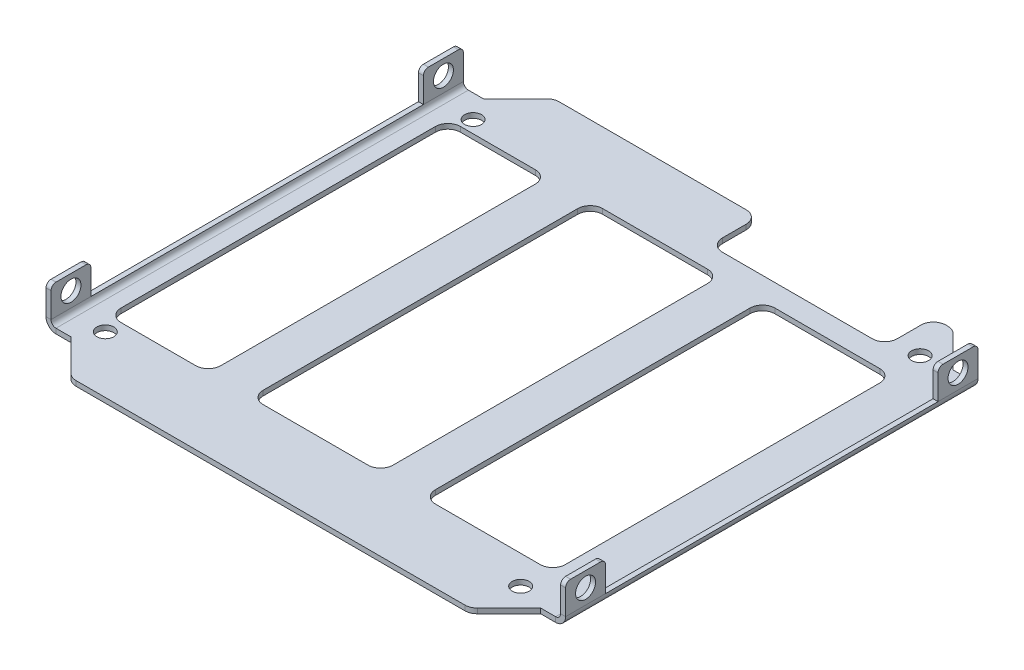
SolidWorks part; units mm, degrees
note: The reader was unsure of these and kept them because the rebuilt part matched: flange length of "Edge-Flange1".
material "6061-T6 (SS)"
ref_plane "Front Plane" through (0, 0, 0) normal (0, 0, 1) x (1, 0, 0)
ref_plane "Top Plane" through (0, 0, 0) normal (0, 1, 0) x (1, 0, 0)
ref_plane "Right Plane" through (0, 0, 0) normal (1, 0, 0) x (0, 0, -1)
sketch "Sketch1" plane through (0, 0, 0) normal (0, 1, 0) x (1, 0, 0)
  line L2 (0, 0) -> (0, 82.6)
  line L4 (104.072, 0) -> (104.072, 82.6)
  line L33 (104.072, 82.6) -> (99.072, 82.6)
  line L37 (5, 82.6) -> (0, 82.6)
  line L38 (5, 82.6) -> (12.0711, 89.6711)
  line L40 (92.0009, 89.6711) -> (99.072, 82.6)
  line L41 (0, 41.3) -> (104.072, 41.3) construction
  line L42 (92.0009, -7.0711) -> (99.072, 0)
  line L43 (12.0711, -7.0711) -> (92.0009, -7.0711)
  line L44 (5, 0) -> (12.0711, -7.0711)
  line L45 (5, 0) -> (0, 0)
  line L46 (104.072, 0) -> (99.072, 0)
  line L47 (88.072, 89.6711) -> (88.072, 79.9211)
  line L48 (88.072, 79.9211) -> (53.072, 79.9211)
  line L49 (53.072, 79.9211) -> (53.072, 89.6711)
  line L50 (53.072, 89.6711) -> (12.0711, 89.6711)
  line L51 (88.072, 89.6711) -> (92.0009, 89.6711)
  line L52 (5, 75.5) -> (5, 7.5)
  line L53 (5, 7.5) -> (94, 7.5)
  line L58 (94, 7.5) -> (94, 75.5)
  line L59 (94, 75.5) -> (5, 75.5)
  dimension "D1" = 82.6
  dimension "D2" = 104.072
  dimension "D3" = 5
  dimension "D4" = 16
  dimension "D5" = 135
  dimension "D6" = 135
  dimension "D7" = 10
  dimension "D8" = 35
  dimension "D9" = 9.75
  dimension "D10" = 41.0009
  dimension "D11" = 68
  dimension "D12" = 89
  dimension "D13" = 7.5
base flange "Base-Flange2" sketch "Sketch1" thickness 1 reverse thickness direction no parameters "D1"=1
edge flange "Edge-Flange1" sketch "Sketch14" flange profiles "Sketch14", "Sketch15" flange angle 90 flange length 8 flange position material inside bend radius 1 thickness 1 relief rectangular parameters "D6"=10, "D8"=1
sketch "Sketch14" plane through (104.072, 0, 0) normal (1, 0, 0) x (0, 0, -1)
  line L0 (0, 0) -> (82.6, 0) construction
  line L1 (0, 0) -> (82.6, 0)
  line L2 (0, 0) -> (0, 7)
  line L3 (0, 7) -> (82.6, 7)
  line L4 (82.6, 7) -> (82.6, 0)
  dimension "D1" = 7
sketch "Sketch15" plane through (0, 0, 0) normal (-1, 0, 0) x (0, 0, 1)
  line L0 (-82.6, 0) -> (0, 0) construction
  line L1 (-82.6, 0) -> (0, 0)
  line L2 (-82.6, 0) -> (-82.6, 7)
  line L3 (-82.6, 7) -> (0, 7)
  line L4 (0, 7) -> (0, 0)
  dimension "D1" = 7
bend "EdgeBend1" bend radius 1 bend angle 90 parameters "D5"=1
bend "EdgeBend2" bend radius 1 bend angle 90 parameters "D5"=2
sketch "Sketch16" plane through (104.072, 0, 0) normal (1, 0, 0) x (0, 0, -1)
  line L0 (82.6, 1) -> (0, 1) construction
  line L1 (8, 8) -> (74.6, 8)
  line L2 (8, 8) -> (8, 1)
  line L3 (8, 1) -> (74.6, 1)
  line L4 (74.6, 8) -> (74.6, 1)
  line L5 (0, 7) -> (0, 1) construction
  line L6 (82.6, 1) -> (82.6, 7) construction
  line L7 (82.6, 7) -> (0, 7) construction
  dimension "D1" = 8
  dimension "D2" = 8
  dimension "D3" = 1
extrude "Cut-Extrude1" cut sketch "Sketch16" against normal through all normal cut yes
fillet "Fillet1" radius 1 8 edges at (0.5, 7, -8) (0.5, 7, 0) (0.5, 7, -74.6) (0.5, 7, -82.6) (103.572, 7, -74.6) (103.572, 7, -82.6) (103.572, 7, 0) (103.572, 7, -8)
sketch "Sketch17" plane through (104.072, 0, 0) normal (1, 0, 0) x (0, 0, -1)
  line L0 (-7.0711, 0) -> (0, 0) construction
  line L1 (0, 6) -> (0, 1) construction
  line L2 (82.6, 0) -> (89.6711, 0) construction
  line L3 (82.6, 1) -> (82.6, 6) construction
  circle A0 centre (4, 4) radius 2
  circle A1 centre (78.6, 4) radius 2
  dimension "D1" = 4
  dimension "D4" = 4
  dimension "D2" = 4
  dimension "D3" = 4
  dimension "D5" = 4
  dimension "D6" = 4
extrude "Cut-Extrude2" cut sketch "Sketch17" against normal through all normal cut yes
hole_wizard "M3 Clearance Hole1" positions "Sketch18" profile "Sketch19" hole size "M3" standard "ANSI Metric" end condition through all
sketch "Sketch18" plane through (0, -1, 0) normal (0, -1, 0) x (-1, 0, 0)
  point P0 (-93.2994, 81.7801)
  point P3 (-7.5694, 77.9701)
  point P6 (-7.5694, 4.3101)
  point P9 (-93.2994, 1.7701)
sketch "Sketch19" plane through (93.2994, -1, -81.7801) normal (1, 0, 0) x (0, 0, -1)
  line L0 (0, 0) -> (0, 8)
  line L1 (0, 8) -> (1.7, 8)
  line L2 (1.7, 8) -> (1.7, 0)
  line L5 (1.7, 0) -> (0, 0)
  line L11 (0, -6.35) -> (0, 107.95) construction
  dimension "Thru Hole Dia." = 3.4
  dimension "Thru Hole Depth" = 8
fillet "Fillet2" radius 2.5 12 edges at (5, -0.5, -7.5) (5, -0.5, -75.5) (12.0711, -0.5, -89.6711) (92.0009, -0.5, -89.6711) (88.072, -0.5, -89.6711) (53.072, -0.5, -89.6711) (53.072, -0.5, -79.9211) (88.072, -0.5, -79.9211) (94, -0.5, -75.5) (94, -0.5, -7.5) (92.0009, -0.5, 7.0711) (12.0711, -0.5, 7.0711)
sketch "Sketch20" plane through (0, -1, 0) normal (0, -1, 0) x (1, 0, 0)
  line L0 (33.5, -75.5) -> (33.5, -7.5)
  line L1 (91.5, -75.5) -> (7.5, -75.5) construction
  line L2 (7.5, -7.5) -> (91.5, -7.5) construction
  line L3 (33.5, -7.5) -> (25, -7.5)
  line L4 (25, -7.5) -> (25, -75.5)
  line L5 (25, -75.5) -> (33.5, -75.5)
  line L6 (59.5, -75.5) -> (59.5, -7.5)
  line L7 (59.5, -7.5) -> (68, -7.5)
  line L8 (68, -7.5) -> (68, -75.5)
  line L9 (68, -75.5) -> (59.5, -75.5)
  line L10 (5, -73) -> (5, -10) construction
  dimension "D1" = 8.5
  dimension "D2" = 8.5
  dimension "D3" = 20
  dimension "D4" = 26
extrude "Boss-Extrude1" add sketch "Sketch20" against normal up to surface (1 mm away) up to face at (93.2994, 0, -83.4801)
fillet "Fillet3" radius 2.5 8 edges at (68, -0.5, -7.5) (33.5, -0.5, -7.5) (25, -0.5, -7.5) (59.5, -0.5, -7.5) (33.5, -0.5, -75.5) (25, -0.5, -75.5) (59.5, -0.5, -75.5) (68, -0.5, -75.5)
sketch "Bend-Lines3" [suppressed] plane through (0, 0, 0) normal (0, 1, 0) x (1, 0, 0)
sketch "Bounding-Box3" [suppressed] plane through (0, 0, 0) normal (0, 1, 0) x (1, 0, 0)
sheet metal parameters "Sheet-Metal2" thickness 1 parameters "D1"=1
flat pattern "Flat-Pattern2" [suppressed]
sketch "Bend-Lines4" plane through (0, 0, 0) normal (0, 1, 0) x (1, 0, 0)
sketch3d "Bounding-Box4" [suppressed]
  line L0 (-135.6338, 86.2583, 0) -> (0, 86.2583, 0) construction
  line L1 (-135.6338, 0, 0) -> (0, 0, 0) construction
  line L2 (-135.6338, 86.2583, 0) -> (-135.6338, 0, 0) construction
  line L3 (0, 86.2583, 0) -> (0, 0, 0) construction
sheet metal parameters "Sheet-Metal3" thickness 1 parameters "D1"=1
flat pattern "Flat-Pattern2"
sketch "Bend-Lines4" plane through (0, 0, 0) normal (0, 1, 0) x (1, 0, 0)
sketch3d "Bounding-Box4" [suppressed]
  line L0 (-135.6338, 86.2583, 0) -> (0, 86.2583, 0) construction
  line L1 (-135.6338, 0, 0) -> (0, 0, 0) construction
  line L2 (-135.6338, 86.2583, 0) -> (-135.6338, 0, 0) construction
  line L3 (0, 86.2583, 0) -> (0, 0, 0) construction
bend of the flat pattern "Flatten-<EdgeBend1>1"
bend of the flat pattern "Flatten-<EdgeBend2>1"
sheet metal parameters "Sheet-Metal4" thickness 1 parameters "D1"=1
flat pattern "Flat-Pattern2"
sketch "Bend-Lines4" plane through (0, 0, 0) normal (0, 1, 0) x (1, 0, 0)
sketch3d "Bounding-Box4" [suppressed]
  line L0 (-135.6338, 86.2583, 0) -> (0, 86.2583, 0) construction
  line L1 (-135.6338, 0, 0) -> (0, 0, 0) construction
  line L2 (-135.6338, 86.2583, 0) -> (-135.6338, 0, 0) construction
  line L3 (0, 86.2583, 0) -> (0, 0, 0) construction
bend of the flat pattern "Flatten-<EdgeBend1>1"
bend of the flat pattern "Flatten-<EdgeBend2>1"
sheet metal parameters "Sheet-Metal5" thickness 1 parameters "D1"=1
flat pattern "Flat-Pattern2"
sketch "Bend-Lines4" plane through (0, 0, 0) normal (0, 1, 0) x (1, 0, 0)
sketch3d "Bounding-Box4" [suppressed]
  line L0 (-135.6338, 86.2583, 0) -> (0, 86.2583, 0) construction
  line L1 (-135.6338, 0, 0) -> (0, 0, 0) construction
  line L2 (-135.6338, 86.2583, 0) -> (-135.6338, 0, 0) construction
  line L3 (0, 86.2583, 0) -> (0, 0, 0) construction
bend of the flat pattern "Flatten-<EdgeBend1>1"
bend of the flat pattern "Flatten-<EdgeBend2>1"
sheet metal parameters "Sheet-Metal6" thickness 1 parameters "D1"=1
flat pattern "Flat-Pattern2"
sketch "Bend-Lines4" plane through (0, 0, 0) normal (0, 1, 0) x (1, 0, 0)
sketch3d "Bounding-Box4" [suppressed]
  line L0 (-135.6338, 86.2583, 0) -> (0, 86.2583, 0) construction
  line L1 (-135.6338, 0, 0) -> (0, 0, 0) construction
  line L2 (-135.6338, 86.2583, 0) -> (-135.6338, 0, 0) construction
  line L3 (0, 86.2583, 0) -> (0, 0, 0) construction
bend of the flat pattern "Flatten-<EdgeBend1>1"
bend of the flat pattern "Flatten-<EdgeBend2>1"
sheet metal parameters "Sheet-Metal7" thickness 1 parameters "D1"=1
flat pattern "Flat-Pattern2"
sketch "Bend-Lines4" plane through (0, 0, 0) normal (0, 1, 0) x (1, 0, 0)
sketch3d "Bounding-Box4" [suppressed]
  line L0 (-135.6338, 86.2583, 0) -> (0, 86.2583, 0) construction
  line L1 (-135.6338, 0, 0) -> (0, 0, 0) construction
  line L2 (-135.6338, 86.2583, 0) -> (-135.6338, 0, 0) construction
  line L3 (0, 86.2583, 0) -> (0, 0, 0) construction
bend of the flat pattern "Flatten-<EdgeBend1>1"
bend of the flat pattern "Flatten-<EdgeBend2>1"
